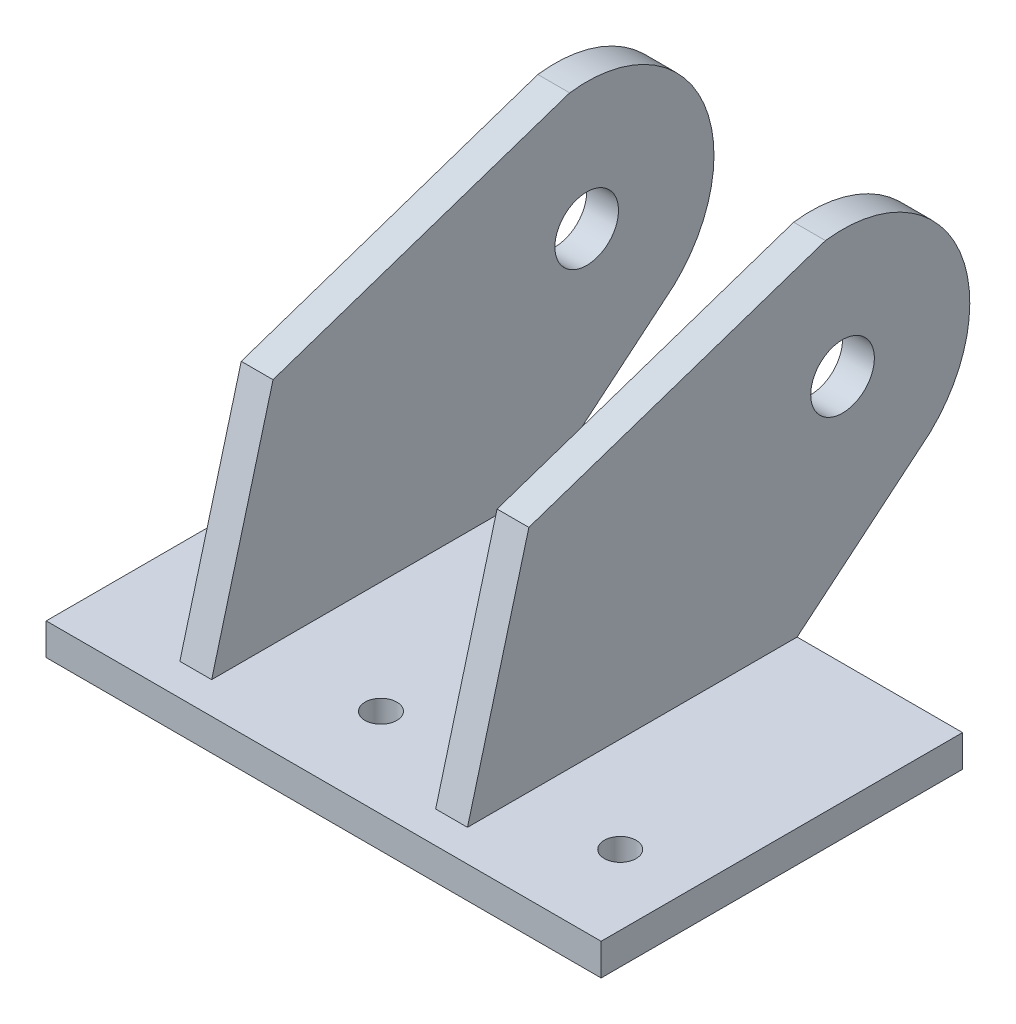
SolidWorks part; units mm, degrees
material "AISI 4130 Steel, annealed at 865C"
ref_plane "Front Plane" through (0, 0, 0) normal (0, 0, 1) x (1, 0, 0)
ref_plane "Top Plane" through (0, 0, 0) normal (0, 1, 0) x (1, 0, 0)
ref_plane "Right Plane" through (0, 0, 0) normal (1, 0, 0) x (0, 0, -1)
sketch "Sketch1" plane through (0, 0, 0) normal (0, 1, 0) x (1, 0, 0)
  line L1 (0, 0) -> (55.372, 0)
  line L2 (0, 0) -> (0, 36.068)
  line L3 (0, 36.068) -> (55.372, 36.068)
  line L4 (55.372, 0) -> (55.372, 36.068)
  line L5 (10.16, 29.718) -> (13.335, 29.718) construction
  line L6 (10.16, 29.718) -> (10.16, 10.414) construction
  line L7 (10.16, 10.414) -> (13.335, 10.414) construction
  line L8 (13.335, 29.718) -> (13.335, 10.414) construction
  line L9 (35.687, 29.718) -> (38.862, 29.718) construction
  line L10 (35.687, 29.718) -> (35.687, 10.414) construction
  line L11 (35.687, 10.414) -> (38.862, 10.414) construction
  line L12 (38.862, 29.718) -> (38.862, 10.414) construction
  circle A0 centre (24.511, 8.89) radius 1.5875
  circle A1 centre (24.511, 26.162) radius 1.5875
  circle A2 centre (48.387, 8.89) radius 1.5875
  dimension "D12" = 3.175
  dimension "D13" = 3.175
  dimension "D14" = 3.175
  dimension "D1" = 55.372
  dimension "D2" = 36.068
  dimension "D3" = 10.16
  dimension "D4" = 6.35
  dimension "D5" = 3.175
  dimension "D6" = 19.304
  dimension "D7" = 22.352
  dimension "D8" = 3.175
  dimension "D9" = 19.304
  dimension "D10" = 11.176
  dimension "D11" = 11.176
  dimension "D15" = 8.89
  dimension "D16" = 17.272
  dimension "D17" = 23.876
extrude "Boss-Extrude1" add sketch "Sketch1" along normal blind 3.175
sketch "Sketch2" plane through (0, 3.175, 0) normal (0, 1, 0) x (1, 0, 0)
  line L0 (0, 0) -> (55.372, 0) construction
  line L1 (10.16, 3.175) -> (13.335, 3.175)
  line L2 (10.16, 3.175) -> (10.16, 53.975)
  line L3 (10.16, 53.975) -> (13.335, 53.975)
  line L4 (13.335, 3.175) -> (13.335, 53.975)
  line L5 (35.687, 3.175) -> (38.862, 3.175)
  line L6 (35.687, 3.175) -> (35.687, 53.975)
  line L7 (35.687, 53.975) -> (38.862, 53.975)
  line L8 (38.862, 3.175) -> (38.862, 53.975)
  circle A1 centre (24.511, 8.89) radius 1.5875 construction
  dimension "D5" = 11.176
  dimension "D1" = 22.352
  dimension "D2" = 3.175
  dimension "D3" = 3.175
  dimension "D4" = 50.8
  dimension "D6" = 3.175
extrude "Boss-Extrude2" add sketch "Sketch2" along normal blind 38.1
sketch "Sketch3" plane through (10.16, 0, 0) normal (-1, 0, 0) x (0, 0, 1)
  circle A0 centre (-40.5975, 23.4355) radius 3.175
  dimension "D1" = 6.35
extrude "Cut-Extrude1" cut sketch "Sketch3" against normal up to surface (28.702 mm away) up to face at (38.862, 18.415, -30.0736)
sketch "Sketch4" plane through (10.16, 0, 0) normal (-1, 0, 0) x (0, 0, 1)
  line L0 (-3.175, 3.175) -> (-3.175, 41.275)
  line L1 (-3.175, 41.275) -> (-53.975, 41.275)
  line L2 (-53.975, 41.275) -> (-53.975, 3.175)
  line L3 (-53.975, 3.175) -> (-36.068, 3.175)
  line L4 (-36.068, 3.175) -> (-49.3422, 14.2257)
  line L5 (-3.175, 3.175) -> (-9.3003, 26.035)
  line L6 (-36.068, 3.175) -> (0, 3.175) construction
  line L7 (-9.3003, 26.035) -> (-38.8983, 36.0214)
  arc A0 (-38.8983, 36.0214) -> (-49.3422, 14.2257) centre (-40.5975, 23.4355) ccw
  point P4 (0, 0)
  dimension "D3" = 12.7
  dimension "D1" = 15
  dimension "D2" = 22.86
  dimension "D4" = 17.272
  dimension "D5" = 29.598
extrude "Cut-Extrude2" cut sketch "Sketch4" against normal through all
